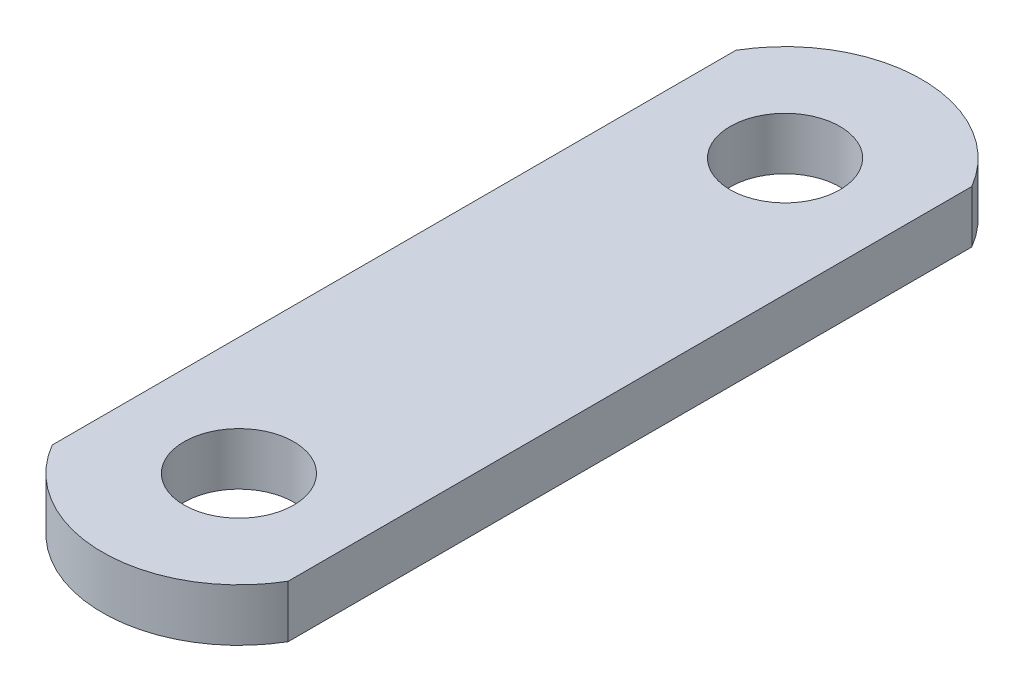
SolidWorks part; units mm, degrees
ref_plane "Front"
ref_plane "Top" through (0, 0, 0) normal (0, 1, 0) x (1, 0, 0)
ref_plane "Right" through (0, 0, 0) normal (1, 0, 0) x (0, 0, -1)
sketch "Sketch1" plane through (0, 0, 0) normal (0, 0, 1) x (1, 0, 0)
  line L1 (0, 0) -> (10.9728, 0)
  line L2 (0, 0) -> (0, 2.4384)
  line L3 (0, 2.4384) -> (10.9728, 2.4384)
  line L4 (10.9728, 0) -> (10.9728, 2.4384)
  dimension "D1" = 2.4384
  dimension "D2" = 10.9728
extrude "Extrude1" add sketch "Sketch1" along normal blind 38.1
sketch "Sketch2" plane through (0, 2.4384, 0) normal (0, 1, 0) x (-1, 0, 0)
  line L0 (0, 6.35) -> (-10.9728, 6.35) construction
  line L1 (0, 38.1) -> (0, 0) construction
  line L2 (-10.9728, 38.1) -> (-10.9728, 0) construction
  line L3 (0, 31.75) -> (-10.9728, 31.75) construction
  line L4 (-10.9728, 0) -> (0, 0) construction
  line L5 (-10.9728, 38.1) -> (0, 38.1) construction
  line L6 (-5.4864, 31.75) -> (-5.4864, 6.35) construction
  dimension "D1" = 6.35
  dimension "D2" = 6.35
hole_wizard "1/4-20 Tapped Hole1" positions "3DSketch1" profile "Sketch3" tap size "1/4-20" standard "Ansi Inch" end condition through all
sketch3d "3DSketch1"
  point P0 (5.4864, 2.4384, 6.35)
  point P2 (5.4864, 2.4384, 31.75)
sketch "Sketch3" plane through (5.4864, 2.4384, 6.35) normal (1, 0, 0) x (0, 0, 1)
  line L0 (0, 0) -> (0, 2.4384)
  line L1 (0, 2.4384) -> (2.5527, 2.4384)
  line L2 (2.5527, 2.4384) -> (2.5527, 0)
  line L5 (2.5527, 0) -> (0, 0)
  line L11 (0, -6.35) -> (0, 107.95) construction
  dimension "Thru Tap Drill Dia." = 5.1054
  dimension "Thru Tap Drill Depth" = 2.4384
cosmetic thread "Cosmetic Thread1" parameters "D1"=2.4384, "D2"=6.35
cosmetic thread "Cosmetic Thread2" parameters "D1"=2.4384, "D2"=6.35
sketch "Sketch4" plane through (0, 2.4384, 0) normal (0, 1, 0) x (-1, 0, 0)
  line L0 (-10.9737, 3.1543) -> (-10.9728, 0)
  line L1 (-10.9728, 0) -> (-5.4864, 0)
  line L2 (-5.4864, 0) -> (0, 0)
  line L3 (0, 0) -> (0, 3.1528)
  line L4 (-10.9737, 34.9457) -> (-10.9728, 38.1)
  line L5 (-10.9728, 38.1) -> (-5.4864, 38.1)
  line L6 (-5.4864, 38.1) -> (0, 38.1)
  line L7 (0, 38.1) -> (0, 34.9472)
  arc A0 (-10.9737, 3.1543) -> (0, 3.1528) centre (-5.4864, 6.35) ccw
  arc A1 (0, 34.9472) -> (-10.9737, 34.9457) centre (-5.4864, 31.75) ccw
extrude "Cut-Extrude1" cut sketch "Sketch4" against normal through all contours L3 A0 L2 | L1 A0 L0 | L4 A1 L5 | L6 A1 L7 region at (9.6787, 2.4384, 0.8857) region at (1.2944, 2.4384, 0.8853) region at (1.2944, 2.4384, 37.2147) region at (9.6787, 2.4384, 37.2143)
